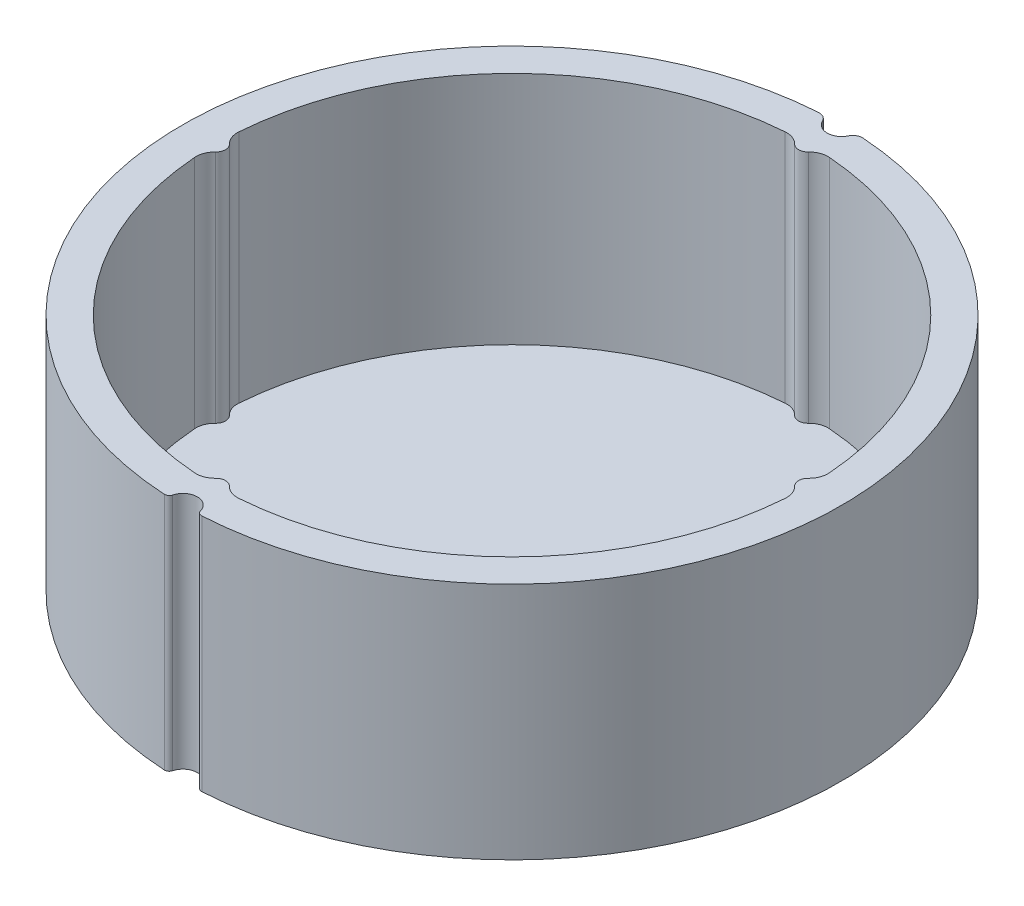
SolidWorks part; units mm, degrees
ref_plane "Front Plane" through (0, 0, 0) normal (0, 0, 1) x (1, 0, 0)
ref_plane "Top Plane" through (0, 0, 0) normal (0, 1, 0) x (1, 0, 0)
ref_plane "Right Plane" through (0, 0, 0) normal (1, 0, 0) x (0, 0, -1)
sketch "Sketch1" plane through (0, 0, 0) normal (0, 1, 0) x (1, 0, 0)
  line L3 (0, 0.002) -> (0, 3.7877) construction
  line L4 (0, 3.7877) -> (2.417, 3.7877)
  line L5 (0, 3.7877) -> (-2.417, 3.7877)
  arc A0 (1.9642, -34.442) -> (34.1982, 4.5552) centre (0, 0.002) ccw
  arc A2 (-2.417, 3.7877) -> (2.417, 3.7877) centre (0, 0.002) ccw
  circle A3 centre (0, 0.002) radius 34.5 construction
  arc A7 (-1.3541, 33.8562) -> (1.3541, 33.8562) centre (0, 34.5015) ccw
  arc A8 (34.1982, 4.5552) -> (2.3241, 34.4236) centre (0, 0.002) ccw
  arc A9 (-2.3241, 34.4236) -> (-34.1982, 4.5552) centre (0, 0.002) ccw
  arc A10 (-34.1982, 4.5552) -> (-1.9642, -34.442) centre (0, 0.002) ccw
  arc A11 (1.3541, 33.8562) -> (2.3241, 34.4236) centre (2.2568, 33.4259) cw
  arc A12 (-1.3541, 33.8562) -> (-2.3241, 34.4236) centre (-2.2568, 33.4259) ccw
  arc A13 (1.4518, -34.0686) -> (-1.4518, -34.0686) centre (0, -34.4457) ccw
  arc A14 (1.4518, -34.0686) -> (1.9642, -34.442) centre (1.9358, -33.9428) ccw
  arc A15 (-1.4518, -34.0686) -> (-1.9642, -34.442) centre (-1.9358, -33.9428) cw
  point P15 (1.4997, 34.4694)
  dimension "D2" = 4.834
  dimension "D3" = 4.4915
  dimension "D4" = 34.5
  dimension "D5" = 1
  dimension "D6" = 1.5
  dimension "D7" = 0.5
  dimension "D11" = 1.4997
sketch "Sketch2" plane through (0, 0, 0) normal (0, 1, 0) x (1, 0, 0)
  arc A0 (-30.9138, -2.3103) -> (-2.3103, -30.9138) centre (0, 0) ccw
  arc A1 (-0.7204, 30.3065) -> (0.7204, 30.3065) centre (0, 31) ccw
  arc A2 (30.3065, 0.7204) -> (30.3065, -0.7204) centre (31, 0) ccw
  arc A3 (0.7204, -30.3065) -> (-0.7204, -30.3065) centre (0, -31) ccw
  arc A4 (-30.3065, -0.7204) -> (-30.3065, 0.7204) centre (-31, 0) ccw
  arc A5 (-2.3103, 30.9138) -> (-30.9138, 2.3103) centre (0, 0) ccw
  arc A6 (30.9138, 2.3103) -> (2.3103, 30.9138) centre (0, 0) ccw
  arc A7 (2.3103, -30.9138) -> (30.9138, -2.3103) centre (0, 0) ccw
  arc A8 (-30.3065, -0.7204) -> (-30.9138, -2.3103) centre (-28.9194, -2.1612) ccw
  arc A9 (-30.3065, 0.7204) -> (-30.9138, 2.3103) centre (-28.9194, 2.1612) cw
  arc A10 (0.7204, -30.3065) -> (2.3103, -30.9138) centre (2.1612, -28.9194) ccw
  arc A11 (-0.7204, -30.3065) -> (-2.3103, -30.9138) centre (-2.1612, -28.9194) cw
  arc A12 (30.3065, 0.7204) -> (30.9138, 2.3103) centre (28.9194, 2.1612) ccw
  arc A13 (30.3065, -0.7204) -> (30.9138, -2.3103) centre (28.9194, -2.1612) cw
  arc A14 (0.7204, 30.3065) -> (2.3103, 30.9138) centre (2.1612, 28.9194) cw
  arc A15 (-0.7204, 30.3065) -> (-2.3103, 30.9138) centre (-2.1612, 28.9194) ccw
  point P21 (0.9999, -30.9839)
  point P26 (30.9839, 0.9999)
  point P33 (-0.9999, 30.9839)
  dimension "D1" = 31
  dimension "D2" = 1
  dimension "D3" = 1
  dimension "D4" = 1
  dimension "D5" = 1
  dimension "D6" = 2
extrude "Boss-Extrude1" add sketch "Sketch1" along normal blind 25 contours A10 A0 A8 A7 A9 A2 L5 L4 region at (2.2155, 0, 33.5591)
extrude "Cut-Extrude2" cut sketch "Sketch2" along normal through all
extrude "Boss-Extrude2" add sketch "Sketch2<2>" along normal blind 0.4
sketch "Sketch2<2>" plane through (0, 0, 0) normal (0, 1, 0) x (1, 0, 0) same geometry as "Sketch2"
